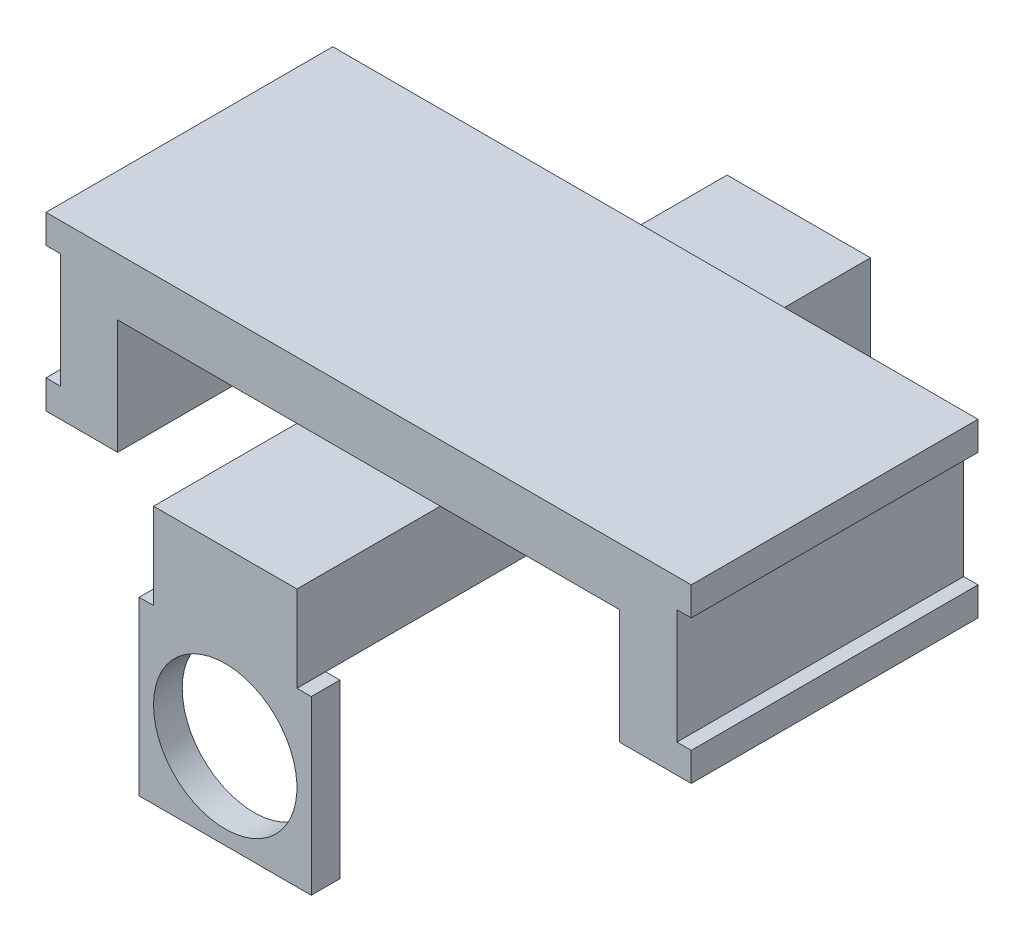
SolidWorks part; units mm, degrees
ref_plane "Front Plane" through (0, 0, 0) normal (0, 0, 1) x (1, 0, 0)
ref_plane "Top Plane" through (0, 0, 0) normal (0, 1, 0) x (1, 0, 0)
ref_plane "Right Plane" through (0, 0, 0) normal (1, 0, 0) x (0, 0, -1)
sketch "Sketch1" plane through (0, 0, 0) normal (0, 1, 0) x (1, 0, 0)
  line L1 (-28.575, -12.7) -> (28.575, -12.7)
  line L2 (-28.575, -12.7) -> (-28.575, 12.7)
  line L3 (-28.575, 12.7) -> (28.575, 12.7)
  line L4 (28.575, -12.7) -> (28.575, 12.7)
  line L5 (-28.575, -12.7) -> (28.575, 12.7) construction
  line L6 (-28.575, 12.7) -> (28.575, -12.7) construction
  point P0 (0, 0)
  dimension "D1" = 25.4
  dimension "D2" = 57.15
extrude "Boss-Extrude1" add sketch "Sketch1" along normal blind 15.24
sketch "Sketch2" plane through (0, 0, 0) normal (0, -1, 0) x (1, 0, 0)
  line L0 (-28.575, 12.7) -> (28.575, 12.7) construction
  line L1 (-22.225, 12.7) -> (22.225, 12.7)
  line L2 (-22.225, 12.7) -> (-22.225, -12.7)
  line L3 (-22.225, -12.7) -> (22.225, -12.7)
  line L4 (22.225, 12.7) -> (22.225, -12.7)
  line L5 (28.575, -12.7) -> (-28.575, -12.7) construction
  line L6 (0, 12.7) -> (0, 0) construction
  line L7 (-28.575, -12.7) -> (-28.575, 12.7) construction
  point P8 (0, 12.7)
  dimension "D1" = 6.35
extrude "Cut-Extrude1" cut sketch "Sketch2" against normal blind 10.16
sketch "Sketch3" plane through (0, 0, 12.7) normal (0, 0, 1) x (1, 0, 0)
  line L0 (-28.575, 15.24) -> (-28.575, 0) construction
  line L1 (-28.575, 12.7) -> (-27.305, 12.7)
  line L2 (-28.575, 12.7) -> (-28.575, 2.54)
  line L3 (-28.575, 2.54) -> (-27.305, 2.54)
  line L4 (-27.305, 12.7) -> (-27.305, 2.54)
  line L5 (28.575, 15.24) -> (28.575, 0) construction
  line L6 (28.575, 12.7) -> (27.305, 12.7)
  line L7 (28.575, 12.7) -> (28.575, 2.54)
  line L8 (28.575, 2.54) -> (27.305, 2.54)
  line L9 (27.305, 12.7) -> (27.305, 2.54)
  line L10 (22.225, 10.16) -> (-22.225, 10.16) construction
  dimension "D1" = 1.27
  dimension "D2" = 10.16
  dimension "D3" = 2.54
extrude "Cut-Extrude2" cut sketch "Sketch3" against normal through all
sketch "Sketch4" plane through (0, 0, 0) normal (0, -1, 0) x (1, 0, 0)
  line L0 (-6.35, 0) -> (6.35, 0) construction
  line L1 (-6.35, -25.4) -> (6.35, -25.4)
  line L2 (-6.35, -25.4) -> (-6.35, 25.4)
  line L3 (-6.35, 25.4) -> (6.35, 25.4)
  line L4 (6.35, -25.4) -> (6.35, 25.4)
  dimension "D2" = 50.8
  dimension "D3" = 12.7
extrude "Boss-Extrude2" add sketch "Sketch4" along normal blind 7.62 from surface starting at face at (0, 10.16, 0)
sketch "Sketch6" plane through (0, 0, -25.4) normal (0, 0, -1) x (-1, 0, 0)
  line L0 (-7.62, 2.54) -> (-7.62, -12.7)
  line L1 (6.35, 2.54) -> (-6.35, 2.54) construction
  line L2 (-7.62, -12.7) -> (7.62, -12.7)
  line L3 (7.62, -12.7) -> (7.62, 2.54)
  line L4 (7.62, 2.54) -> (-7.62, 2.54)
  line L5 (-7.62, 2.54) -> (7.62, -12.7) construction
  line L6 (6.35, 2.54) -> (-6.35, 2.54) construction
  circle A0 centre (0, -5.08) radius 6.35
  point P9 (0, 2.54)
  dimension "D1" = 12.7
  dimension "D2" = 15.24
  dimension "D3" = 15.24
extrude "Boss-Extrude3" add sketch "Sketch6" against normal blind 2.54
mirror "Mirror1" about plane through (0, 0, 0) normal (0, 0, 1) of "Boss-Extrude3"
